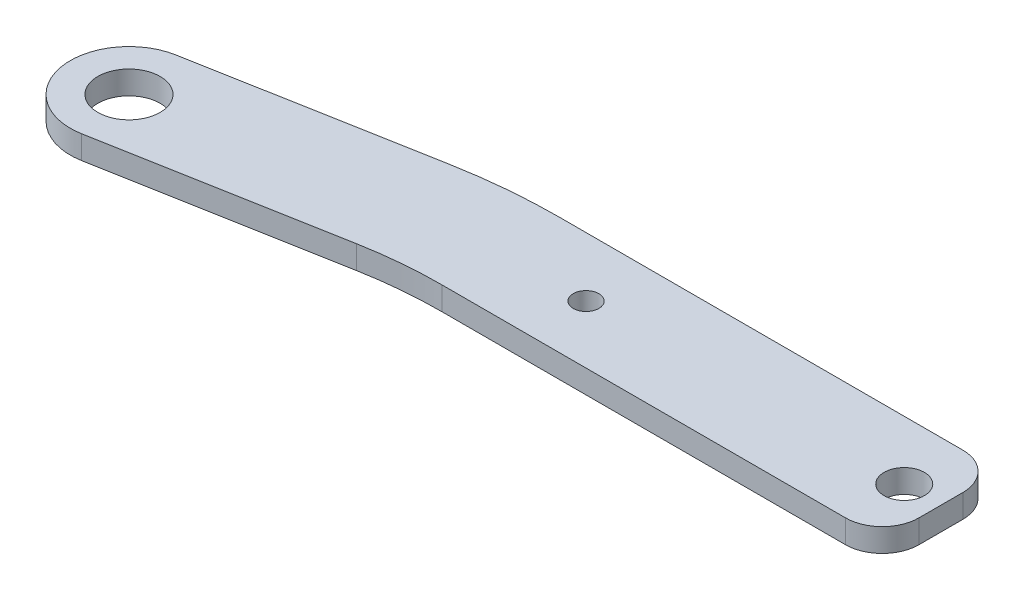
SolidWorks part; units mm, degrees
material "Copper"
ref_plane "Front Plane" through (0, 0, 0) normal (0, 0, 1) x (1, 0, 0)
ref_plane "Top Plane" through (0, 0, 0) normal (0, 1, 0) x (1, 0, 0)
ref_plane "Right Plane" through (0, 0, 0) normal (1, 0, 0) x (0, 0, -1)
sketch "Sketch1" plane through (0, 0, 0) normal (0, 1, 0) x (1, 0, 0)
  line L0 (-1.4287, 7.8714) -> (30.29, 13.6283)
  line L1 (43.8622, 14.85) -> (98.8622, 14.85)
  line L2 (98.8622, -1.15) -> (43.8622, -1.15)
  line L3 (33.1473, -2.1145) -> (1.4287, -7.8714)
  line L4 (103.8622, 3.85) -> (103.8622, 9.85)
  circle A0 centre (0, 0) radius 4.25
  circle A1 centre (98.8622, 6.85) radius 2.75
  arc A5 (1.4287, -7.8714) -> (-1.4287, 7.8714) centre (0, 0) cw
  arc A6 (43.8622, -1.15) -> (33.1473, -2.1145) centre (43.8622, -61.15) ccw
  arc A7 (43.8622, 14.85) -> (30.29, 13.6283) centre (43.8622, -61.15) ccw
  arc A9 (98.8622, -1.15) -> (103.8622, 3.85) centre (98.8622, 3.85) ccw
  arc A10 (103.8622, 9.85) -> (98.8622, 14.85) centre (98.8622, 9.85) ccw
  point P24 (103.8622, 6.85)
  dimension "D1" = 8.5
  dimension "D2" = 5.5
  dimension "D3" = 16
  dimension "D4" = 55
  dimension "D5" = 60
  dimension "D6" = 5
  dimension "D7" = 5
extrude "Boss-Extrude1" add sketch "Sketch1" along normal blind 3.175
sketch "Sketch2" plane through (0, 0, 0) normal (0, -1, 0) x (1, 0, 0)
  circle A0 centre (55.5622, -6.7594) radius 1.75
extrude "Cut-Extrude1" cut sketch "Sketch2" against normal through all
